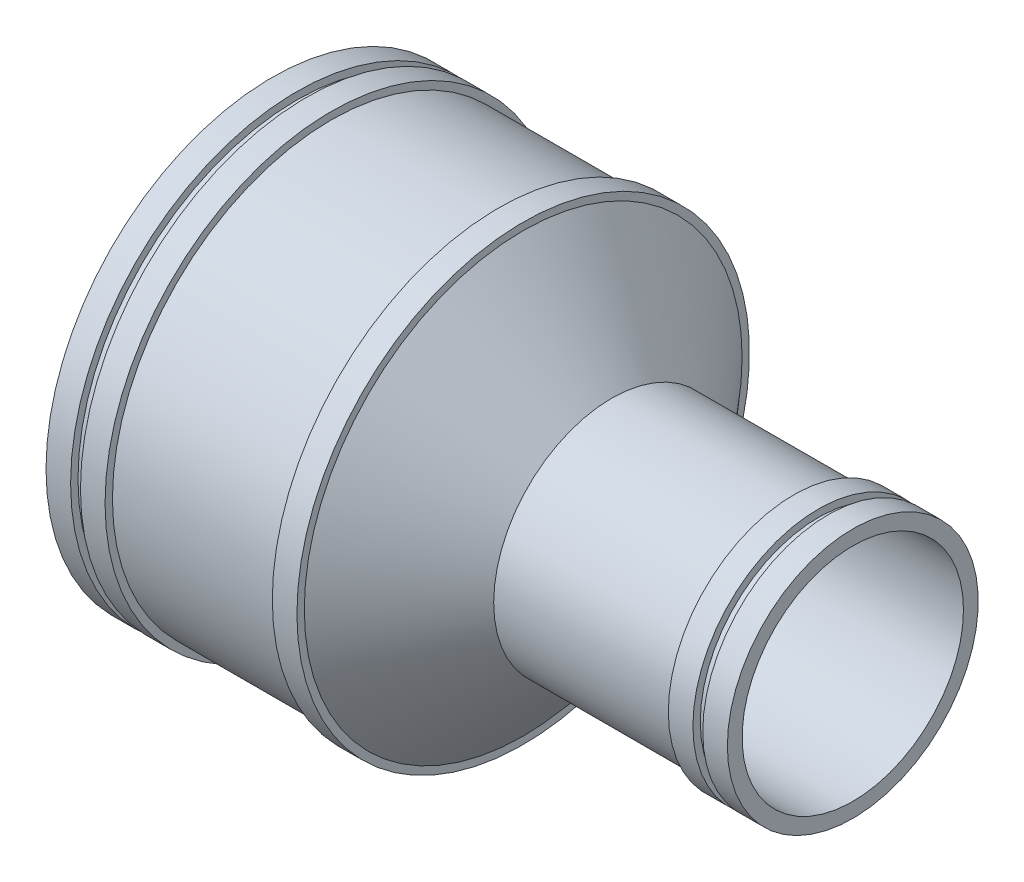
SolidWorks part; units mm, degrees
ref_plane "Front Plane" through (0, 0, 0) normal (0, 0, 1) x (1, 0, 0)
ref_plane "Top Plane" through (0, 0, 0) normal (0, 1, 0) x (1, 0, 0)
ref_plane "Right Plane" through (0, 0, 0) normal (1, 0, 0) x (0, 0, -1)
sketch "Skeleton" plane through (0, 0, 0) normal (1, 0, 0) x (0, 0, -1)
  circle A0 centre (0, 0) radius 38.1 construction
  circle A1 centre (0, 0) radius 41.5
  circle A2 centre (0, 0) radius 44.5
  circle A3 centre (0, 0) radius 22
  circle A4 centre (0, 0) radius 24
  circle A5 centre (0, 0) radius 20.25
  dimension "D1" = 76.2
  dimension "D2" = 83
  dimension "D3" = 89
  dimension "D4" = 44
  dimension "D5" = 48
  dimension "D6" = 40.5
extrude "Boss-Extrude1" add sketch "Skeleton" along normal blind 51 contours A2 A1 region at (0, 0, 43.2413)
extrude "Boss-Extrude2" add sketch "Skeleton<3>" along normal blind 49 from offset 69 separate body contours A4 A3 region at (0, 0, 23.3212)
sketch "Skeleton<3>" plane through (0, 0, 0) normal (1, 0, 0) x (0, 0, -1) same geometry as "Skeleton"
loft "Loft1" add section edge at (51, 0, -44.5) section edge at (69, 0, -24) connector at (51, 41.4772, 16.1213) connector at (69, 22.1558, 9.2262)
loft "Cut-Loft1" cut section edge at (69, 0, -22) section edge at (51, 0, -41.5) connector at (69, 9.1163, -20.0223) connector at (51, 27.3661, -31.1985)
sketch "Sketch4" plane through (0, 0, 0) normal (0, 0, 1) x (1, 0, 0)
  line L0 (51, 44.5) -> (0, 44.5) construction
  line L1 (51, 44.5) -> (0, 44.5)
  line L2 (0, 44.5) -> (0, 46)
  line L3 (0, 46) -> (5, 46)
  line L4 (5, 46) -> (5, 44.5)
  line L5 (5, 44.5) -> (7, 44.5)
  line L6 (7, 44.5) -> (7, 46)
  line L7 (7, 46) -> (12, 46)
  line L8 (12, 46) -> (12, 44.5)
  line L9 (12, 44.5) -> (0, 44.5)
  line L10 (0, 0) -> (130.5111, 0) construction
  line L11 (106, 24) -> (106, 25.5)
  line L12 (51, 44.5) -> (46, 44.5)
  line L13 (51, 44.5) -> (51, 46)
  line L14 (51, 46) -> (46, 46)
  line L15 (46, 44.5) -> (46, 46)
  line L16 (106, 25.5) -> (111, 25.5)
  line L17 (111, 25.5) -> (111, 24)
  line L18 (111, 24) -> (113, 24)
  line L19 (113, 24) -> (113, 25.5)
  line L20 (113, 25.5) -> (118, 25.5)
  line L21 (118, 25.5) -> (118, 24)
  line L22 (118, 24) -> (106, 24)
  point P23 (0, 0)
  dimension "D1" = 1.5
  dimension "D2" = 5
  dimension "D3" = 2
  dimension "D4" = 5
  dimension "D5" = 1.5
  dimension "D6" = 5
  dimension "D7" = 2
revolve "Revolve1" add sketch "Sketch4" angle 360 about L10 region at (2.5, 45.25, 0) region at (9.5, 45.25, 0) region at (48.5, 45.25, 0) region at (115.5, 24.75, 0) region at (108.5, 24.75, 0)
sketch "Sketch6" plane through (118, 0, 0) normal (1, 0, 0) x (0, 0, -1)
  circle A0 centre (0, 0) radius 22.5
  dimension "D1" = 45
extrude "Cut-Extrude1" cut sketch "Sketch6" against normal blind 39
